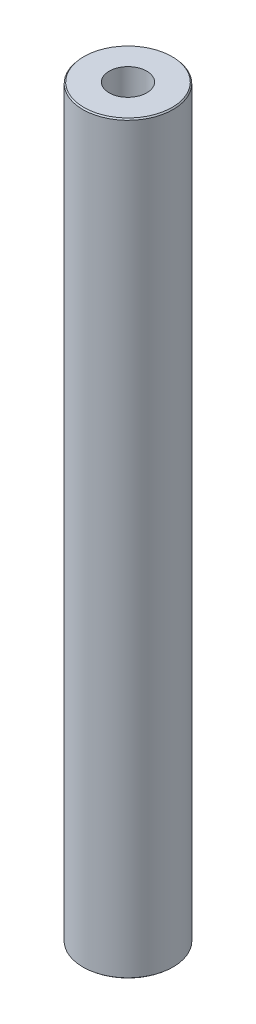
SolidWorks part; units mm, degrees
ref_plane "Front Plane" through (0, 0, 0) normal (0, 0, 1) x (1, 0, 0)
ref_plane "Top Plane" through (0, 0, 0) normal (0, 1, 0) x (1, 0, 0)
ref_plane "Right Plane" through (0, 0, 0) normal (1, 0, 0) x (0, 0, -1)
sketch "Sketch1" plane through (0, 0, 0) normal (0, 1, 0) x (1, 0, 0)
  circle A0 centre (0, 0) radius 20
  dimension "SHAFT_OD" = 40
extrude "Boss-Extrude1" add sketch "Sketch1" along normal blind 330.0125
sketch "Sketch2" plane through (0, 0, 0) normal (0, 1, 0) x (1, 0, 0)
  circle A0 centre (0, 0) radius 8.3361
  dimension "BORE_D" = 16.6722
extrude "Cut-Extrude1" cut sketch "Sketch2" along normal through all
chamfer "Chamfer1" distance 0.5681 angle 39.912 2 edges at (0, 330.0125, 20) (0, 0, 20) first distance on face at (0, 330.0125, 20) first distance on face at (0, 0, 8.3361)
